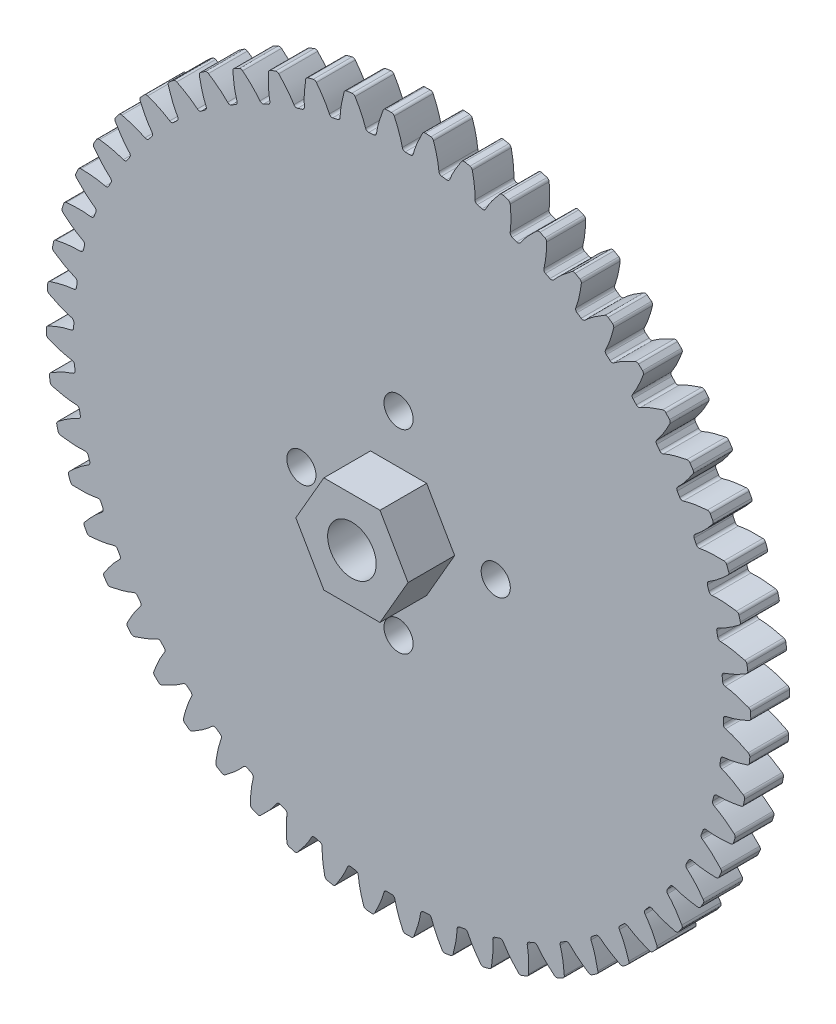
SolidWorks part; units mm, degrees
ref_plane "前视基准面" through (0, 0, 0) normal (0, 0, 1) x (1, 0, 0)
ref_plane "上视基准面" through (0, 0, 0) normal (0, 1, 0) x (1, 0, 0)
ref_plane "右视基准面" through (0, 0, 0) normal (1, 0, 0) x (0, 0, -1)
sketch "草图1" plane through (0, 0, 0) normal (0, 0, 1) x (1, 0, 0)
  circle B0 centre (0, 0) radius 6.5
  circle B1 centre (-10, 0) radius 0.925
  circle B2 centre (0, 10) radius 0.925
  circle B3 centre (0, -10) radius 0.925
  circle B4 centre (10, 0) radius 0.925
  arc B5 (3.3275, 36.097) -> (2.766, 36.1443) centre (0, 0) ccw
  arc B6 (1.1925, 33.4162) -> (0.9378, 33.4243) centre (0, 0) ccw
  arc B7 (4.152, 33.4242) -> (4.4218, 33.1438) centre (4.4631, 33.4536) ccw
  arc B8 (1.1925, 33.4162) -> (1.5054, 33.6474) centre (1.2036, 33.7285) ccw
  arc B9 (2.766, 36.1443) -> (2.4649, 35.9769) centre (2.7421, 35.8327) ccw
  arc B10 (3.5963, 35.8815) -> (3.3275, 36.097) centre (3.2988, 35.7858) ccw
  arc B11 (4.6742, 33.1092) -> (4.4218, 33.1438) centre (0, 0) ccw
  arc B12 (7.3482, 35.4974) -> (6.7954, 35.6074) centre (0, 0) ccw
  arc B13 (4.9264, 33.0726) -> (4.6742, 33.1092) centre (0, 0) ccw
  arc B14 (7.8682, 32.7491) -> (8.1049, 32.4404) centre (8.1807, 32.7435) ccw
  arc B15 (4.9264, 33.0726) -> (5.2633, 33.2673) centre (4.9725, 33.3817) ccw
  arc B16 (6.7954, 35.6074) -> (6.4775, 35.4747) centre (6.7369, 35.3004) ccw
  arc B17 (7.5912, 35.2532) -> (7.3482, 35.4974) centre (7.2848, 35.1914) ccw
  arc B18 (8.3519, 32.3776) -> (8.1049, 32.4404) centre (0, 0) ccw
  arc B19 (11.2764, 34.4515) -> (10.7395, 34.6226) centre (0, 0) ccw
  arc B20 (8.5984, 32.3131) -> (8.3519, 32.3776) centre (0, 0) ccw
  arc B21 (11.4855, 31.6623) -> (11.6861, 31.3289) centre (11.7953, 31.6217) ccw
  arc B22 (8.5984, 32.3131) -> (8.9549, 32.4688) centre (8.6787, 32.6151) ccw
  arc B23 (10.7395, 34.6226) -> (10.4087, 34.5264) centre (10.6469, 34.3242) ccw
  arc B24 (11.4905, 34.1816) -> (11.2764, 34.4515) centre (11.1792, 34.1545) ccw
  arc B25 (11.9245, 31.2389) -> (11.6861, 31.3289) centre (0, 0) ccw
  arc B26 (15.0629, 32.9723) -> (14.5485, 33.2025) centre (0, 0) ccw
  arc B27 (12.1622, 31.1472) -> (11.9245, 31.2389) centre (0, 0) ccw
  arc B28 (14.9583, 30.1772) -> (15.1204, 29.8235) centre (15.2617, 30.1022) ccw
  arc B29 (12.1622, 31.1472) -> (12.534, 31.262) centre (12.2759, 31.4383) ccw
  arc B30 (14.5485, 33.2025) -> (14.2089, 33.1439) centre (14.423, 32.9163) ccw
  arc B31 (15.2454, 32.6801) -> (15.0629, 32.9723) centre (14.933, 32.6881) ccw
  arc B32 (15.3472, 29.7074) -> (15.1204, 29.8235) centre (0, 0) ccw
  arc B33 (18.6599, 31.0785) -> (18.1745, 31.3648) centre (0, 0) ccw
  arc B34 (15.5731, 29.5896) -> (15.3472, 29.7074) centre (0, 0) ccw
  arc B35 (18.243, 28.3127) -> (18.3645, 27.943) centre (18.5361, 28.2042) ccw
  arc B36 (15.5731, 29.5896) -> (15.9554, 29.6621) centre (15.7187, 29.8661) ccw
  arc B37 (18.1745, 31.3648) -> (17.8305, 31.3446) centre (18.0178, 31.0944) ccw
  arc B38 (18.8086, 30.7677) -> (18.6599, 31.0785) centre (18.499, 30.8106) ccw
  arc B39 (18.5769, 27.8023) -> (18.3645, 27.943) centre (0, 0) ccw
  arc B40 (22.0222, 28.7938) -> (21.5719, 29.1327) centre (0, 0) ccw
  arc B41 (18.7882, 27.6599) -> (18.5769, 27.8023) centre (0, 0) ccw
  arc B42 (21.2983, 26.0921) -> (21.3776, 25.7112) centre (21.5774, 25.9514) ccw
  arc B43 (18.7882, 27.6599) -> (19.1762, 27.6892) centre (18.9638, 27.9184) ccw
  arc B44 (21.5719, 29.1327) -> (21.2279, 29.1511) centre (21.386, 28.8815) ccw
  arc B45 (22.1352, 28.4683) -> (22.0222, 28.7938) centre (21.8324, 28.5456) ccw
  arc B46 (21.5729, 25.5475) -> (21.3776, 25.7112) centre (0, 0) ccw
  arc B47 (25.1076, 26.1471) -> (24.6981, 26.5342) centre (0, 0) ccw
  arc B48 (21.767, 25.3824) -> (21.5729, 25.5475) centre (0, 0) ccw
  arc B49 (24.0858, 23.5433) -> (24.1219, 23.156) centre (24.3474, 23.3724) ccw
  arc B50 (21.767, 25.3824) -> (22.1558, 25.368) centre (21.9704, 25.6196) ccw
  arc B51 (24.6981, 26.5342) -> (24.3583, 26.5911) centre (24.4852, 26.3055) ccw
  arc B52 (25.1834, 25.811) -> (25.1076, 26.1471) centre (24.8912, 25.9217) ccw
  arc B53 (24.2977, 22.9715) -> (24.1219, 23.156) centre (0, 0) ccw
  arc B54 (27.8773, 23.1715) -> (27.5137, 23.6021) centre (0, 0) ccw
  arc B55 (24.4721, 22.7856) -> (24.2977, 22.9715) centre (0, 0) ccw
  arc B56 (26.5704, 20.6986) -> (26.5629, 20.3096) centre (26.8112, 20.4994) ccw
  arc B57 (24.4721, 22.7856) -> (24.8568, 22.7278) centre (24.7008, 22.9986) ccw
  arc B58 (27.5137, 23.6021) -> (27.1824, 23.6966) centre (27.2765, 23.3986) ccw
  arc B59 (27.915, 22.829) -> (27.8773, 23.1715) centre (27.637, 22.9717) ccw
  arc B60 (26.7169, 20.1065) -> (26.5629, 20.3096) centre (0, 0) ccw
  arc B61 (30.2964, 19.9045) -> (29.9833, 20.3731) centre (0, 0) ccw
  arc B62 (26.8694, 19.9024) -> (26.7169, 20.1065) centre (0, 0) ccw
  arc B63 (28.7208, 17.5935) -> (28.6698, 17.2077) centre (28.9378, 17.3686) ccw
  arc B64 (26.8694, 19.9024) -> (27.2452, 19.8018) centre (27.1205, 20.0884) ccw
  arc B65 (29.9833, 20.3731) -> (29.6647, 20.5041) centre (29.7248, 20.1975) ccw
  arc B66 (30.2955, 19.56) -> (30.2964, 19.9045) centre (30.0352, 19.7329) ccw
  arc B67 (28.8001, 16.9888) -> (28.6698, 17.2077) centre (0, 0) ccw
  arc B68 (32.3345, 16.3872) -> (32.0759, 16.8879) centre (0, 0) ccw
  arc B69 (28.9288, 16.7688) -> (28.8001, 16.9888) centre (0, 0) ccw
  arc B70 (30.5101, 14.2671) -> (30.4162, 13.8895) centre (30.7005, 14.0194) ccw
  arc B71 (28.9288, 16.7688) -> (29.291, 16.6268) centre (29.1991, 16.9255) ccw
  arc B72 (32.0759, 16.8879) -> (31.7739, 17.0538) centre (31.7993, 16.7423) ccw
  arc B73 (32.2951, 16.045) -> (32.3345, 16.3872) centre (32.0558, 16.246) ccw
  arc B74 (30.5212, 13.6574) -> (30.4162, 13.8895) centre (0, 0) ccw
  arc B75 (33.966, 12.6639) -> (33.765, 13.1904) centre (0, 0) ccw
  arc B76 (30.6244, 13.4244) -> (30.5212, 13.6574) centre (0, 0) ccw
  arc B77 (31.9156, 10.7614) -> (31.7801, 10.3967) centre (32.0771, 10.4938) ccw
  arc B78 (30.6244, 13.4244) -> (30.9685, 13.2427) centre (30.9106, 13.5498) ccw
  arc B79 (33.765, 13.1904) -> (33.4835, 13.389) centre (33.4739, 13.0767) ccw
  arc B80 (33.8885, 12.3282) -> (33.966, 12.6639) centre (33.6732, 12.5547) ccw
  arc B81 (31.8584, 10.1542) -> (31.7801, 10.3967) centre (0, 0) ccw
  arc B82 (35.1703, 8.7813) -> (35.0296, 9.327) centre (0, 0) ccw
  arc B83 (31.9349, 9.9111) -> (31.8584, 10.1542) centre (0, 0) ccw
  arc B84 (32.9199, 7.1203) -> (32.7443, 6.7731) centre (33.0504, 6.8364) ccw
  arc B85 (31.9349, 9.9111) -> (32.2564, 9.6921) centre (32.2333, 10.0037) ccw
  arc B86 (35.0296, 9.327) -> (34.7721, 9.5559) centre (34.7276, 9.2466) ccw
  arc B87 (35.0557, 8.4564) -> (35.1703, 8.7813) centre (34.8671, 8.7056) ccw
  arc B88 (32.795, 6.5233) -> (32.7443, 6.7731) centre (0, 0) ccw
  arc B89 (35.9324, 4.7882) -> (35.8536, 5.3463) centre (0, 0) ccw
  arc B90 (32.8438, 6.2732) -> (32.795, 6.5233) centre (0, 0) ccw
  arc B91 (33.5101, 3.3897) -> (33.2968, 3.0643) centre (33.608, 3.0929) ccw
  arc B92 (32.8438, 6.2732) -> (33.1388, 6.0196) centre (33.1507, 6.3319) ccw
  arc B93 (35.8536, 5.3463) -> (35.6234, 5.6026) centre (35.5445, 5.3002) ccw
  arc B94 (35.7821, 4.4782) -> (35.9324, 4.7882) centre (35.6226, 4.747) ccw
  arc B95 (33.3192, 2.8104) -> (33.2968, 3.0643) centre (0, 0) ccw
  arc B96 (36.2425, 0.735) -> (36.2267, 1.2983) centre (0, 0) ccw
  arc B97 (33.3396, 2.5565) -> (33.3192, 2.8104) centre (0, 0) ccw
  arc B98 (33.6789, -0.3836) -> (33.4305, -0.6831) centre (33.743, -0.6894) ccw
  arc B99 (33.3396, 2.5565) -> (33.6044, 2.2714) centre (33.6512, 2.5803) ccw
  arc B100 (36.2267, 1.2983) -> (36.0266, 1.5788) centre (35.9144, 1.2871) ccw
  arc B101 (36.0585, 0.4437) -> (36.2425, 0.735) centre (35.9301, 0.7286) ccw
  arc B102 (33.4243, -0.9378) -> (33.4305, -0.6831) centre (0, 0) ccw
  arc B103 (36.097, -3.3275) -> (36.1443, -2.766) centre (0, 0) ccw
  arc B104 (33.4162, -1.1925) -> (33.4243, -0.9378) centre (0, 0) ccw
  arc B105 (33.4242, -4.152) -> (33.1438, -4.4218) centre (33.4536, -4.4631) ccw
  arc B106 (33.4162, -1.1925) -> (33.6474, -1.5054) centre (33.7285, -1.2036) ccw
  arc B107 (36.1443, -2.766) -> (35.9769, -2.4649) centre (35.8327, -2.7421) ccw
  arc B108 (35.8815, -3.5963) -> (36.097, -3.3275) centre (35.7858, -3.2988) ccw
  arc B109 (33.1092, -4.6742) -> (33.1438, -4.4218) centre (0, 0) ccw
  arc B110 (35.4974, -7.3482) -> (35.6074, -6.7954) centre (0, 0) ccw
  arc B111 (33.0726, -4.9264) -> (33.1092, -4.6742) centre (0, 0) ccw
  arc B112 (32.7491, -7.8682) -> (32.4404, -8.1049) centre (32.7435, -8.1807) ccw
  arc B113 (33.0726, -4.9264) -> (33.2673, -5.2633) centre (33.3817, -4.9725) ccw
  arc B114 (35.6074, -6.7954) -> (35.4747, -6.4775) centre (35.3004, -6.7369) ccw
  arc B115 (35.2532, -7.5912) -> (35.4974, -7.3482) centre (35.1914, -7.2848) ccw
  arc B116 (32.3776, -8.3519) -> (32.4404, -8.1049) centre (0, 0) ccw
  arc B117 (34.4515, -11.2764) -> (34.6226, -10.7395) centre (0, 0) ccw
  arc B118 (32.3131, -8.5984) -> (32.3776, -8.3519) centre (0, 0) ccw
  arc B119 (31.6623, -11.4855) -> (31.3289, -11.6861) centre (31.6217, -11.7953) ccw
  arc B120 (32.3131, -8.5984) -> (32.4688, -8.9549) centre (32.6151, -8.6787) ccw
  arc B121 (34.6226, -10.7395) -> (34.5264, -10.4087) centre (34.3242, -10.6469) ccw
  arc B122 (34.1816, -11.4905) -> (34.4515, -11.2764) centre (34.1545, -11.1792) ccw
  arc B123 (31.2389, -11.9245) -> (31.3289, -11.6861) centre (0, 0) ccw
  arc B124 (32.9723, -15.0629) -> (33.2025, -14.5485) centre (0, 0) ccw
  arc B125 (31.1472, -12.1622) -> (31.2389, -11.9245) centre (0, 0) ccw
  arc B126 (30.1772, -14.9583) -> (29.8235, -15.1204) centre (30.1022, -15.2617) ccw
  arc B127 (31.1472, -12.1622) -> (31.262, -12.534) centre (31.4383, -12.2759) ccw
  arc B128 (33.2025, -14.5485) -> (33.1439, -14.2089) centre (32.9163, -14.423) ccw
  arc B129 (32.6801, -15.2454) -> (32.9723, -15.0629) centre (32.6881, -14.933) ccw
  arc B130 (29.7074, -15.3472) -> (29.8235, -15.1204) centre (0, 0) ccw
  arc B131 (31.0785, -18.6599) -> (31.3648, -18.1745) centre (0, 0) ccw
  arc B132 (29.5896, -15.5731) -> (29.7074, -15.3472) centre (0, 0) ccw
  arc B133 (28.3127, -18.243) -> (27.943, -18.3645) centre (28.2042, -18.5361) ccw
  arc B134 (29.5896, -15.5731) -> (29.6621, -15.9554) centre (29.8661, -15.7187) ccw
  arc B135 (31.3648, -18.1745) -> (31.3446, -17.8305) centre (31.0944, -18.0178) ccw
  arc B136 (30.7677, -18.8086) -> (31.0785, -18.6599) centre (30.8106, -18.499) ccw
  arc B137 (27.8023, -18.5769) -> (27.943, -18.3645) centre (0, 0) ccw
  arc B138 (28.7938, -22.0222) -> (29.1327, -21.5719) centre (0, 0) ccw
  arc B139 (27.6599, -18.7882) -> (27.8023, -18.5769) centre (0, 0) ccw
  arc B140 (26.0921, -21.2983) -> (25.7112, -21.3776) centre (25.9514, -21.5774) ccw
  arc B141 (27.6599, -18.7882) -> (27.6892, -19.1762) centre (27.9184, -18.9638) ccw
  arc B142 (29.1327, -21.5719) -> (29.1511, -21.2279) centre (28.8815, -21.386) ccw
  arc B143 (28.4683, -22.1352) -> (28.7938, -22.0222) centre (28.5456, -21.8324) ccw
  arc B144 (25.5475, -21.5729) -> (25.7112, -21.3776) centre (0, 0) ccw
  arc B145 (26.1471, -25.1076) -> (26.5342, -24.6981) centre (0, 0) ccw
  arc B146 (25.3824, -21.767) -> (25.5475, -21.5729) centre (0, 0) ccw
  arc B147 (23.5433, -24.0858) -> (23.156, -24.1219) centre (23.3724, -24.3474) ccw
  arc B148 (25.3824, -21.767) -> (25.368, -22.1558) centre (25.6196, -21.9704) ccw
  arc B149 (26.5342, -24.6981) -> (26.5911, -24.3583) centre (26.3055, -24.4852) ccw
  arc B150 (25.811, -25.1834) -> (26.1471, -25.1076) centre (25.9217, -24.8912) ccw
  arc B151 (22.9715, -24.2977) -> (23.156, -24.1219) centre (0, 0) ccw
  arc B152 (23.1715, -27.8773) -> (23.6021, -27.5137) centre (0, 0) ccw
  arc B153 (22.7856, -24.4721) -> (22.9715, -24.2977) centre (0, 0) ccw
  arc B154 (20.6986, -26.5704) -> (20.3096, -26.5629) centre (20.4994, -26.8112) ccw
  arc B155 (22.7856, -24.4721) -> (22.7278, -24.8568) centre (22.9986, -24.7008) ccw
  arc B156 (23.6021, -27.5137) -> (23.6966, -27.1824) centre (23.3986, -27.2765) ccw
  arc B157 (22.829, -27.915) -> (23.1715, -27.8773) centre (22.9717, -27.637) ccw
  arc B158 (20.1065, -26.7169) -> (20.3096, -26.5629) centre (0, 0) ccw
  arc B159 (19.9045, -30.2964) -> (20.3731, -29.9833) centre (0, 0) ccw
  arc B160 (19.9024, -26.8694) -> (20.1065, -26.7169) centre (0, 0) ccw
  arc B161 (17.5935, -28.7208) -> (17.2077, -28.6698) centre (17.3686, -28.9378) ccw
  arc B162 (19.9024, -26.8694) -> (19.8018, -27.2452) centre (20.0884, -27.1205) ccw
  arc B163 (20.3731, -29.9833) -> (20.5041, -29.6647) centre (20.1975, -29.7248) ccw
  arc B164 (19.56, -30.2955) -> (19.9045, -30.2964) centre (19.7329, -30.0352) ccw
  arc B165 (16.9888, -28.8001) -> (17.2077, -28.6698) centre (0, 0) ccw
  arc B166 (16.3872, -32.3345) -> (16.8879, -32.0759) centre (0, 0) ccw
  arc B167 (16.7688, -28.9288) -> (16.9888, -28.8001) centre (0, 0) ccw
  arc B168 (14.2671, -30.5101) -> (13.8895, -30.4162) centre (14.0194, -30.7005) ccw
  arc B169 (16.7688, -28.9288) -> (16.6268, -29.291) centre (16.9255, -29.1991) ccw
  arc B170 (16.8879, -32.0759) -> (17.0538, -31.7739) centre (16.7423, -31.7993) ccw
  arc B171 (16.045, -32.2951) -> (16.3872, -32.3345) centre (16.246, -32.0558) ccw
  arc B172 (13.6574, -30.5212) -> (13.8895, -30.4162) centre (0, 0) ccw
  arc B173 (12.6639, -33.966) -> (13.1904, -33.765) centre (0, 0) ccw
  arc B174 (13.4244, -30.6244) -> (13.6574, -30.5212) centre (0, 0) ccw
  arc B175 (10.7614, -31.9156) -> (10.3967, -31.7801) centre (10.4938, -32.0771) ccw
  arc B176 (13.4244, -30.6244) -> (13.2427, -30.9685) centre (13.5498, -30.9106) ccw
  arc B177 (13.1904, -33.765) -> (13.389, -33.4835) centre (13.0767, -33.4739) ccw
  arc B178 (12.3282, -33.8885) -> (12.6639, -33.966) centre (12.5547, -33.6732) ccw
  arc B179 (10.1542, -31.8584) -> (10.3967, -31.7801) centre (0, 0) ccw
  arc B180 (8.7813, -35.1703) -> (9.327, -35.0296) centre (0, 0) ccw
  arc B181 (9.9111, -31.9349) -> (10.1542, -31.8584) centre (0, 0) ccw
  arc B182 (7.1203, -32.9199) -> (6.7731, -32.7443) centre (6.8364, -33.0504) ccw
  arc B183 (9.9111, -31.9349) -> (9.6921, -32.2564) centre (10.0037, -32.2333) ccw
  arc B184 (9.327, -35.0296) -> (9.5559, -34.7721) centre (9.2466, -34.7276) ccw
  arc B185 (8.4564, -35.0557) -> (8.7813, -35.1703) centre (8.7056, -34.8671) ccw
  arc B186 (6.5233, -32.795) -> (6.7731, -32.7443) centre (0, 0) ccw
  arc B187 (4.7882, -35.9324) -> (5.3463, -35.8536) centre (0, 0) ccw
  arc B188 (6.2732, -32.8438) -> (6.5233, -32.795) centre (0, 0) ccw
  arc B189 (3.3897, -33.5101) -> (3.0643, -33.2968) centre (3.0929, -33.608) ccw
  arc B190 (6.2732, -32.8438) -> (6.0196, -33.1388) centre (6.3319, -33.1507) ccw
  arc B191 (5.3463, -35.8536) -> (5.6026, -35.6234) centre (5.3002, -35.5445) ccw
  arc B192 (4.4782, -35.7821) -> (4.7882, -35.9324) centre (4.747, -35.6226) ccw
  arc B193 (2.8104, -33.3192) -> (3.0643, -33.2968) centre (0, 0) ccw
  arc B194 (0.735, -36.2425) -> (1.2983, -36.2267) centre (0, 0) ccw
  arc B195 (2.5565, -33.3396) -> (2.8104, -33.3192) centre (0, 0) ccw
  arc B196 (-0.3836, -33.6789) -> (-0.6831, -33.4305) centre (-0.6894, -33.743) ccw
  arc B197 (2.5565, -33.3396) -> (2.2714, -33.6044) centre (2.5803, -33.6512) ccw
  arc B198 (1.2983, -36.2267) -> (1.5788, -36.0266) centre (1.2871, -35.9144) ccw
  arc B199 (0.4437, -36.0585) -> (0.735, -36.2425) centre (0.7286, -35.9301) ccw
  arc B200 (-0.9378, -33.4243) -> (-0.6831, -33.4305) centre (0, 0) ccw
  arc B201 (-3.3275, -36.097) -> (-2.766, -36.1443) centre (0, 0) ccw
  arc B202 (-1.1925, -33.4162) -> (-0.9378, -33.4243) centre (0, 0) ccw
  arc B203 (-4.152, -33.4242) -> (-4.4218, -33.1438) centre (-4.4631, -33.4536) ccw
  arc B204 (-1.1925, -33.4162) -> (-1.5054, -33.6474) centre (-1.2036, -33.7285) ccw
  arc B205 (-2.766, -36.1443) -> (-2.4649, -35.9769) centre (-2.7421, -35.8327) ccw
  arc B206 (-3.5963, -35.8815) -> (-3.3275, -36.097) centre (-3.2988, -35.7858) ccw
  arc B207 (-4.6742, -33.1092) -> (-4.4218, -33.1438) centre (0, 0) ccw
  arc B208 (-7.3482, -35.4974) -> (-6.7954, -35.6074) centre (0, 0) ccw
  arc B209 (-4.9264, -33.0726) -> (-4.6742, -33.1092) centre (0, 0) ccw
  arc B210 (-7.8682, -32.7491) -> (-8.1049, -32.4404) centre (-8.1807, -32.7435) ccw
  arc B211 (-4.9264, -33.0726) -> (-5.2633, -33.2673) centre (-4.9725, -33.3817) ccw
  arc B212 (-6.7954, -35.6074) -> (-6.4775, -35.4747) centre (-6.7369, -35.3004) ccw
  arc B213 (-7.5912, -35.2532) -> (-7.3482, -35.4974) centre (-7.2848, -35.1914) ccw
  arc B214 (-8.3519, -32.3776) -> (-8.1049, -32.4404) centre (0, 0) ccw
  arc B215 (-11.2764, -34.4515) -> (-10.7395, -34.6226) centre (0, 0) ccw
  arc B216 (-8.5984, -32.3131) -> (-8.3519, -32.3776) centre (0, 0) ccw
  arc B217 (-11.4855, -31.6623) -> (-11.6861, -31.3289) centre (-11.7953, -31.6217) ccw
  arc B218 (-8.5984, -32.3131) -> (-8.9549, -32.4688) centre (-8.6787, -32.6151) ccw
  arc B219 (-10.7395, -34.6226) -> (-10.4087, -34.5264) centre (-10.6469, -34.3242) ccw
  arc B220 (-11.4905, -34.1816) -> (-11.2764, -34.4515) centre (-11.1792, -34.1545) ccw
  arc B221 (-11.9245, -31.2389) -> (-11.6861, -31.3289) centre (0, 0) ccw
  arc B222 (-15.0629, -32.9723) -> (-14.5485, -33.2025) centre (0, 0) ccw
  arc B223 (-12.1622, -31.1472) -> (-11.9245, -31.2389) centre (0, 0) ccw
  arc B224 (-14.9583, -30.1772) -> (-15.1204, -29.8235) centre (-15.2617, -30.1022) ccw
  arc B225 (-12.1622, -31.1472) -> (-12.534, -31.262) centre (-12.2759, -31.4383) ccw
  arc B226 (-14.5485, -33.2025) -> (-14.2089, -33.1439) centre (-14.423, -32.9163) ccw
  arc B227 (-15.2454, -32.6801) -> (-15.0629, -32.9723) centre (-14.933, -32.6881) ccw
  arc B228 (-15.3472, -29.7074) -> (-15.1204, -29.8235) centre (0, 0) ccw
  arc B229 (-18.6599, -31.0785) -> (-18.1745, -31.3648) centre (0, 0) ccw
  arc B230 (-15.5731, -29.5896) -> (-15.3472, -29.7074) centre (0, 0) ccw
  arc B231 (-18.243, -28.3127) -> (-18.3645, -27.943) centre (-18.5361, -28.2042) ccw
  arc B232 (-15.5731, -29.5896) -> (-15.9554, -29.6621) centre (-15.7187, -29.8661) ccw
  arc B233 (-18.1745, -31.3648) -> (-17.8305, -31.3446) centre (-18.0178, -31.0944) ccw
  arc B234 (-18.8086, -30.7677) -> (-18.6599, -31.0785) centre (-18.499, -30.8106) ccw
  arc B235 (-18.5769, -27.8023) -> (-18.3645, -27.943) centre (0, 0) ccw
  arc B236 (-22.0222, -28.7938) -> (-21.5719, -29.1327) centre (0, 0) ccw
  arc B237 (-18.7882, -27.6599) -> (-18.5769, -27.8023) centre (0, 0) ccw
  arc B238 (-21.2983, -26.0921) -> (-21.3776, -25.7112) centre (-21.5774, -25.9514) ccw
  arc B239 (-18.7882, -27.6599) -> (-19.1762, -27.6892) centre (-18.9638, -27.9184) ccw
  arc B240 (-21.5719, -29.1327) -> (-21.2279, -29.1511) centre (-21.386, -28.8815) ccw
  arc B241 (-22.1352, -28.4683) -> (-22.0222, -28.7938) centre (-21.8324, -28.5456) ccw
  arc B242 (-21.5729, -25.5475) -> (-21.3776, -25.7112) centre (0, 0) ccw
  arc B243 (-25.1076, -26.1471) -> (-24.6981, -26.5342) centre (0, 0) ccw
  arc B244 (-21.767, -25.3824) -> (-21.5729, -25.5475) centre (0, 0) ccw
  arc B245 (-24.0858, -23.5433) -> (-24.1219, -23.156) centre (-24.3474, -23.3724) ccw
  arc B246 (-21.767, -25.3824) -> (-22.1558, -25.368) centre (-21.9704, -25.6196) ccw
  arc B247 (-24.6981, -26.5342) -> (-24.3583, -26.5911) centre (-24.4852, -26.3055) ccw
  arc B248 (-25.1834, -25.811) -> (-25.1076, -26.1471) centre (-24.8912, -25.9217) ccw
  arc B249 (-24.2977, -22.9715) -> (-24.1219, -23.156) centre (0, 0) ccw
  arc B250 (-27.8773, -23.1715) -> (-27.5137, -23.6021) centre (0, 0) ccw
  arc B251 (-24.4721, -22.7856) -> (-24.2977, -22.9715) centre (0, 0) ccw
  arc B252 (-26.5704, -20.6986) -> (-26.5629, -20.3096) centre (-26.8112, -20.4994) ccw
  arc B253 (-24.4721, -22.7856) -> (-24.8568, -22.7278) centre (-24.7008, -22.9986) ccw
  arc B254 (-27.5137, -23.6021) -> (-27.1824, -23.6966) centre (-27.2765, -23.3986) ccw
  arc B255 (-27.915, -22.829) -> (-27.8773, -23.1715) centre (-27.637, -22.9717) ccw
  arc B256 (-26.7169, -20.1065) -> (-26.5629, -20.3096) centre (0, 0) ccw
  arc B257 (-30.2964, -19.9045) -> (-29.9833, -20.3731) centre (0, 0) ccw
  arc B258 (-26.8694, -19.9024) -> (-26.7169, -20.1065) centre (0, 0) ccw
  arc B259 (-28.7208, -17.5935) -> (-28.6698, -17.2077) centre (-28.9378, -17.3686) ccw
  arc B260 (-26.8694, -19.9024) -> (-27.2452, -19.8018) centre (-27.1205, -20.0884) ccw
  arc B261 (-29.9833, -20.3731) -> (-29.6647, -20.5041) centre (-29.7248, -20.1975) ccw
  arc B262 (-30.2955, -19.56) -> (-30.2964, -19.9045) centre (-30.0352, -19.7329) ccw
  arc B263 (-28.8001, -16.9888) -> (-28.6698, -17.2077) centre (0, 0) ccw
  arc B264 (-32.3345, -16.3872) -> (-32.0759, -16.8879) centre (0, 0) ccw
  arc B265 (-28.9288, -16.7688) -> (-28.8001, -16.9888) centre (0, 0) ccw
  arc B266 (-30.5101, -14.2671) -> (-30.4162, -13.8895) centre (-30.7005, -14.0194) ccw
  arc B267 (-28.9288, -16.7688) -> (-29.291, -16.6268) centre (-29.1991, -16.9255) ccw
  arc B268 (-32.0759, -16.8879) -> (-31.7739, -17.0538) centre (-31.7993, -16.7423) ccw
  arc B269 (-32.2951, -16.045) -> (-32.3345, -16.3872) centre (-32.0558, -16.246) ccw
  arc B270 (-30.5212, -13.6574) -> (-30.4162, -13.8895) centre (0, 0) ccw
  arc B271 (-33.966, -12.6639) -> (-33.765, -13.1904) centre (0, 0) ccw
  arc B272 (-30.6244, -13.4244) -> (-30.5212, -13.6574) centre (0, 0) ccw
  arc B273 (-31.9156, -10.7614) -> (-31.7801, -10.3967) centre (-32.0771, -10.4938) ccw
  arc B274 (-30.6244, -13.4244) -> (-30.9685, -13.2427) centre (-30.9106, -13.5498) ccw
  arc B275 (-33.765, -13.1904) -> (-33.4835, -13.389) centre (-33.4739, -13.0767) ccw
  arc B276 (-33.8885, -12.3282) -> (-33.966, -12.6639) centre (-33.6732, -12.5547) ccw
  arc B277 (-31.8584, -10.1542) -> (-31.7801, -10.3967) centre (0, 0) ccw
  arc B278 (-35.1703, -8.7813) -> (-35.0296, -9.327) centre (0, 0) ccw
  arc B279 (-31.9349, -9.9111) -> (-31.8584, -10.1542) centre (0, 0) ccw
  arc B280 (-32.9199, -7.1203) -> (-32.7443, -6.7731) centre (-33.0504, -6.8364) ccw
  arc B281 (-31.9349, -9.9111) -> (-32.2564, -9.6921) centre (-32.2333, -10.0037) ccw
  arc B282 (-35.0296, -9.327) -> (-34.7721, -9.5559) centre (-34.7276, -9.2466) ccw
  arc B283 (-35.0557, -8.4564) -> (-35.1703, -8.7813) centre (-34.8671, -8.7056) ccw
  arc B284 (-32.795, -6.5233) -> (-32.7443, -6.7731) centre (0, 0) ccw
  arc B285 (-35.9324, -4.7882) -> (-35.8536, -5.3463) centre (0, 0) ccw
  arc B286 (-32.8438, -6.2732) -> (-32.795, -6.5233) centre (0, 0) ccw
  arc B287 (-33.5101, -3.3897) -> (-33.2968, -3.0643) centre (-33.608, -3.0929) ccw
  arc B288 (-32.8438, -6.2732) -> (-33.1388, -6.0196) centre (-33.1507, -6.3319) ccw
  arc B289 (-35.8536, -5.3463) -> (-35.6234, -5.6026) centre (-35.5445, -5.3002) ccw
  arc B290 (-35.7821, -4.4782) -> (-35.9324, -4.7882) centre (-35.6226, -4.747) ccw
  arc B291 (-33.3192, -2.8104) -> (-33.2968, -3.0643) centre (0, 0) ccw
  arc B292 (-36.2425, -0.735) -> (-36.2267, -1.2983) centre (0, 0) ccw
  arc B293 (-33.3396, -2.5565) -> (-33.3192, -2.8104) centre (0, 0) ccw
  arc B294 (-33.6789, 0.3836) -> (-33.4305, 0.6831) centre (-33.743, 0.6894) ccw
  arc B295 (-33.3396, -2.5565) -> (-33.6044, -2.2714) centre (-33.6512, -2.5803) ccw
  arc B296 (-36.2267, -1.2983) -> (-36.0266, -1.5788) centre (-35.9144, -1.2871) ccw
  arc B297 (-36.0585, -0.4437) -> (-36.2425, -0.735) centre (-35.9301, -0.7286) ccw
  arc B298 (-33.4243, 0.9378) -> (-33.4305, 0.6831) centre (0, 0) ccw
  arc B299 (-36.097, 3.3275) -> (-36.1443, 2.766) centre (0, 0) ccw
  arc B300 (-33.4162, 1.1925) -> (-33.4243, 0.9378) centre (0, 0) ccw
  arc B301 (-33.4242, 4.152) -> (-33.1438, 4.4218) centre (-33.4536, 4.4631) ccw
  arc B302 (-33.4162, 1.1925) -> (-33.6474, 1.5054) centre (-33.7285, 1.2036) ccw
  arc B303 (-36.1443, 2.766) -> (-35.9769, 2.4649) centre (-35.8327, 2.7421) ccw
  arc B304 (-35.8815, 3.5963) -> (-36.097, 3.3275) centre (-35.7858, 3.2988) ccw
  arc B305 (-33.1092, 4.6742) -> (-33.1438, 4.4218) centre (0, 0) ccw
  arc B306 (-35.4974, 7.3482) -> (-35.6074, 6.7954) centre (0, 0) ccw
  arc B307 (-33.0726, 4.9264) -> (-33.1092, 4.6742) centre (0, 0) ccw
  arc B308 (-32.7491, 7.8682) -> (-32.4404, 8.1049) centre (-32.7435, 8.1807) ccw
  arc B309 (-33.0726, 4.9264) -> (-33.2673, 5.2633) centre (-33.3817, 4.9725) ccw
  arc B310 (-35.6074, 6.7954) -> (-35.4747, 6.4775) centre (-35.3004, 6.7369) ccw
  arc B311 (-35.2532, 7.5912) -> (-35.4974, 7.3482) centre (-35.1914, 7.2848) ccw
  arc B312 (-32.3776, 8.3519) -> (-32.4404, 8.1049) centre (0, 0) ccw
  arc B313 (-34.4515, 11.2764) -> (-34.6226, 10.7395) centre (0, 0) ccw
  arc B314 (-32.3131, 8.5984) -> (-32.3776, 8.3519) centre (0, 0) ccw
  arc B315 (-31.6623, 11.4855) -> (-31.3289, 11.6861) centre (-31.6217, 11.7953) ccw
  arc B316 (-32.3131, 8.5984) -> (-32.4688, 8.9549) centre (-32.6151, 8.6787) ccw
  arc B317 (-34.6226, 10.7395) -> (-34.5264, 10.4087) centre (-34.3242, 10.6469) ccw
  arc B318 (-34.1816, 11.4905) -> (-34.4515, 11.2764) centre (-34.1545, 11.1792) ccw
  arc B319 (-31.2389, 11.9245) -> (-31.3289, 11.6861) centre (0, 0) ccw
  arc B320 (-32.9723, 15.0629) -> (-33.2025, 14.5485) centre (0, 0) ccw
  arc B321 (-31.1472, 12.1622) -> (-31.2389, 11.9245) centre (0, 0) ccw
  arc B322 (-30.1772, 14.9583) -> (-29.8235, 15.1204) centre (-30.1022, 15.2617) ccw
  arc B323 (-31.1472, 12.1622) -> (-31.262, 12.534) centre (-31.4383, 12.2759) ccw
  arc B324 (-33.2025, 14.5485) -> (-33.1439, 14.2089) centre (-32.9163, 14.423) ccw
  arc B325 (-32.6801, 15.2454) -> (-32.9723, 15.0629) centre (-32.6881, 14.933) ccw
  arc B326 (-29.7074, 15.3472) -> (-29.8235, 15.1204) centre (0, 0) ccw
  arc B327 (-31.0785, 18.6599) -> (-31.3648, 18.1745) centre (0, 0) ccw
  arc B328 (-29.5896, 15.5731) -> (-29.7074, 15.3472) centre (0, 0) ccw
  arc B329 (-28.3127, 18.243) -> (-27.943, 18.3645) centre (-28.2042, 18.5361) ccw
  arc B330 (-29.5896, 15.5731) -> (-29.6621, 15.9554) centre (-29.8661, 15.7187) ccw
  arc B331 (-31.3648, 18.1745) -> (-31.3446, 17.8305) centre (-31.0944, 18.0178) ccw
  arc B332 (-30.7677, 18.8086) -> (-31.0785, 18.6599) centre (-30.8106, 18.499) ccw
  arc B333 (-27.8023, 18.5769) -> (-27.943, 18.3645) centre (0, 0) ccw
  arc B334 (-28.7938, 22.0222) -> (-29.1327, 21.5719) centre (0, 0) ccw
  arc B335 (-27.6599, 18.7882) -> (-27.8023, 18.5769) centre (0, 0) ccw
  arc B336 (-26.0921, 21.2983) -> (-25.7112, 21.3776) centre (-25.9514, 21.5774) ccw
  arc B337 (-27.6599, 18.7882) -> (-27.6892, 19.1762) centre (-27.9184, 18.9638) ccw
  arc B338 (-29.1327, 21.5719) -> (-29.1511, 21.2279) centre (-28.8815, 21.386) ccw
  arc B339 (-28.4683, 22.1352) -> (-28.7938, 22.0222) centre (-28.5456, 21.8324) ccw
  arc B340 (-25.5475, 21.5729) -> (-25.7112, 21.3776) centre (0, 0) ccw
  arc B341 (-26.1471, 25.1076) -> (-26.5342, 24.6981) centre (0, 0) ccw
  arc B342 (-25.3824, 21.767) -> (-25.5475, 21.5729) centre (0, 0) ccw
  arc B343 (-23.5433, 24.0858) -> (-23.156, 24.1219) centre (-23.3724, 24.3474) ccw
  arc B344 (-25.3824, 21.767) -> (-25.368, 22.1558) centre (-25.6196, 21.9704) ccw
  arc B345 (-26.5342, 24.6981) -> (-26.5911, 24.3583) centre (-26.3055, 24.4852) ccw
  arc B346 (-25.811, 25.1834) -> (-26.1471, 25.1076) centre (-25.9217, 24.8912) ccw
  arc B347 (-22.9715, 24.2977) -> (-23.156, 24.1219) centre (0, 0) ccw
  arc B348 (-23.1715, 27.8773) -> (-23.6021, 27.5137) centre (0, 0) ccw
  arc B349 (-22.7856, 24.4721) -> (-22.9715, 24.2977) centre (0, 0) ccw
  arc B350 (-20.6986, 26.5704) -> (-20.3096, 26.5629) centre (-20.4994, 26.8112) ccw
  arc B351 (-22.7856, 24.4721) -> (-22.7278, 24.8568) centre (-22.9986, 24.7008) ccw
  arc B352 (-23.6021, 27.5137) -> (-23.6966, 27.1824) centre (-23.3986, 27.2765) ccw
  arc B353 (-22.829, 27.915) -> (-23.1715, 27.8773) centre (-22.9717, 27.637) ccw
  arc B354 (-20.1065, 26.7169) -> (-20.3096, 26.5629) centre (0, 0) ccw
  arc B355 (-19.9045, 30.2964) -> (-20.3731, 29.9833) centre (0, 0) ccw
  arc B356 (-19.9024, 26.8694) -> (-20.1065, 26.7169) centre (0, 0) ccw
  arc B357 (-17.5935, 28.7208) -> (-17.2077, 28.6698) centre (-17.3686, 28.9378) ccw
  arc B358 (-19.9024, 26.8694) -> (-19.8018, 27.2452) centre (-20.0884, 27.1205) ccw
  arc B359 (-20.3731, 29.9833) -> (-20.5041, 29.6647) centre (-20.1975, 29.7248) ccw
  arc B360 (-19.56, 30.2955) -> (-19.9045, 30.2964) centre (-19.7329, 30.0352) ccw
  arc B361 (-16.9888, 28.8001) -> (-17.2077, 28.6698) centre (0, 0) ccw
  arc B362 (-16.3872, 32.3345) -> (-16.8879, 32.0759) centre (0, 0) ccw
  arc B363 (-16.7688, 28.9288) -> (-16.9888, 28.8001) centre (0, 0) ccw
  arc B364 (-14.2671, 30.5101) -> (-13.8895, 30.4162) centre (-14.0194, 30.7005) ccw
  arc B365 (-16.7688, 28.9288) -> (-16.6268, 29.291) centre (-16.9255, 29.1991) ccw
  arc B366 (-16.8879, 32.0759) -> (-17.0538, 31.7739) centre (-16.7423, 31.7993) ccw
  arc B367 (-16.045, 32.2951) -> (-16.3872, 32.3345) centre (-16.246, 32.0558) ccw
  arc B368 (-13.6574, 30.5212) -> (-13.8895, 30.4162) centre (0, 0) ccw
  arc B369 (-12.6639, 33.966) -> (-13.1904, 33.765) centre (0, 0) ccw
  arc B370 (-13.4244, 30.6244) -> (-13.6574, 30.5212) centre (0, 0) ccw
  arc B371 (-10.7614, 31.9156) -> (-10.3967, 31.7801) centre (-10.4938, 32.0771) ccw
  arc B372 (-13.4244, 30.6244) -> (-13.2427, 30.9685) centre (-13.5498, 30.9106) ccw
  arc B373 (-13.1904, 33.765) -> (-13.389, 33.4835) centre (-13.0767, 33.4739) ccw
  arc B374 (-12.3282, 33.8885) -> (-12.6639, 33.966) centre (-12.5547, 33.6732) ccw
  arc B375 (-10.1542, 31.8584) -> (-10.3967, 31.7801) centre (0, 0) ccw
  arc B376 (-8.7813, 35.1703) -> (-9.327, 35.0296) centre (0, 0) ccw
  arc B377 (-9.9111, 31.9349) -> (-10.1542, 31.8584) centre (0, 0) ccw
  arc B378 (-7.1203, 32.9199) -> (-6.7731, 32.7443) centre (-6.8364, 33.0504) ccw
  arc B379 (-9.9111, 31.9349) -> (-9.6921, 32.2564) centre (-10.0037, 32.2333) ccw
  arc B380 (-9.327, 35.0296) -> (-9.5559, 34.7721) centre (-9.2466, 34.7276) ccw
  arc B381 (-8.4564, 35.0557) -> (-8.7813, 35.1703) centre (-8.7056, 34.8671) ccw
  arc B382 (-6.5233, 32.795) -> (-6.7731, 32.7443) centre (0, 0) ccw
  arc B383 (-4.7882, 35.9324) -> (-5.3463, 35.8536) centre (0, 0) ccw
  arc B384 (-6.2732, 32.8438) -> (-6.5233, 32.795) centre (0, 0) ccw
  arc B385 (-3.3897, 33.5101) -> (-3.0643, 33.2968) centre (-3.0929, 33.608) ccw
  arc B386 (-6.2732, 32.8438) -> (-6.0196, 33.1388) centre (-6.3319, 33.1507) ccw
  arc B387 (-5.3463, 35.8536) -> (-5.6026, 35.6234) centre (-5.3002, 35.5445) ccw
  arc B388 (-4.4782, 35.7821) -> (-4.7882, 35.9324) centre (-4.747, 35.6226) ccw
  arc B389 (-2.8104, 33.3192) -> (-3.0643, 33.2968) centre (0, 0) ccw
  arc B390 (0.9378, 33.4243) -> (0.6831, 33.4305) centre (0, 0) ccw
  arc B391 (-0.4437, 36.0585) -> (-0.735, 36.2425) centre (-0.7286, 35.9301) ccw
  arc B392 (-1.2983, 36.2267) -> (-1.5788, 36.0266) centre (-1.2871, 35.9144) ccw
  arc B393 (-2.5565, 33.3396) -> (-2.2714, 33.6044) centre (-2.5803, 33.6512) ccw
  arc B394 (0.3836, 33.6789) -> (0.6831, 33.4305) centre (0.6894, 33.743) ccw
  arc B395 (-2.5565, 33.3396) -> (-2.8104, 33.3192) centre (0, 0) ccw
  arc B396 (-0.735, 36.2425) -> (-1.2983, 36.2267) centre (0, 0) ccw
  spline B397 degree 3 poles (2.4649, 35.9769) (2.3009, 35.6616) (1.9902, 35.0512) (1.6861, 34.2646) (1.5461, 33.7988) (1.5054, 33.6474) knots 0.205794 0.205794 0.205794 0.205794 1.271237 2.259978 2.73007 2.73007 2.73007 2.73007
  spline B398 degree 3 poles (3.5963, 35.8815) (3.7051, 35.5432) (3.9092, 34.8894) (4.0772, 34.0629) (4.1373, 33.5802) (4.152, 33.4242) knots 0.205794 0.205794 0.205794 0.205794 1.271237 2.259978 2.73007 2.73007 2.73007 2.73007
  spline B399 degree 3 poles (6.4775, 35.4747) (6.2793, 35.1797) (5.9022, 34.608) (5.512, 33.8604) (5.3206, 33.4132) (5.2633, 33.2673) knots 0.205794 0.205794 0.205794 0.205794 1.271237 2.259978 2.73007 2.73007 2.73007 2.73007
  spline B400 degree 3 poles (7.5912, 35.2532) (7.6614, 34.9048) (7.791, 34.2323) (7.8654, 33.3922) (7.871, 32.9059) (7.8682, 32.7491) knots 0.205794 0.205794 0.205794 0.205794 1.271237 2.259978 2.73007 2.73007 2.73007 2.73007
  spline B401 degree 3 poles (10.4087, 34.5264) (10.1787, 34.2555) (9.7399, 33.7296) (9.2685, 33.0303) (9.0283, 32.6073) (8.9549, 32.4688) knots 0.205794 0.205794 0.205794 0.205794 1.271237 2.259978 2.73007 2.73007 2.73007 2.73007
  spline B402 degree 3 poles (11.4905, 34.1816) (11.5213, 33.8275) (11.5748, 33.1447) (11.5547, 32.3016) (11.5058, 31.8177) (11.4855, 31.6623) knots 0.205794 0.205794 0.205794 0.205794 1.271237 2.259978 2.73007 2.73007 2.73007 2.73007
  spline B403 degree 3 poles (14.2089, 33.1439) (13.9501, 32.9004) (13.4552, 32.4269) (12.9084, 31.7849) (12.6224, 31.3915) (12.534, 31.262) knots 0.205794 0.205794 0.205794 0.205794 1.271237 2.259978 2.73007 2.73007 2.73007 2.73007
  spline B404 degree 3 poles (15.2454, 32.6801) (15.2364, 32.3249) (15.2131, 31.6403) (15.0987, 30.8048) (14.9959, 30.3294) (14.9583, 30.1772) knots 0.205794 0.205794 0.205794 0.205794 1.271237 2.259978 2.73007 2.73007 2.73007 2.73007
  spline B405 degree 3 poles (17.8305, 31.3446) (17.5461, 31.1317) (17.0013, 30.7165) (16.386, 30.1398) (16.0577, 29.7808) (15.9554, 29.6621) knots 0.205794 0.205794 0.205794 0.205794 1.271237 2.259978 2.73007 2.73007 2.73007 2.73007
  spline B406 degree 3 poles (18.8086, 30.7677) (18.7598, 30.4157) (18.66, 29.7381) (18.4528, 28.9206) (18.2975, 28.4597) (18.243, 28.3127) knots 0.205794 0.205794 0.205794 0.205794 1.271237 2.259978 2.73007 2.73007 2.73007 2.73007
  spline B407 degree 3 poles (21.2279, 29.1511) (20.9214, 28.9714) (20.3335, 28.6199) (19.6576, 28.1156) (19.2912, 27.7957) (19.1762, 27.6892) knots 0.205794 0.205794 0.205794 0.205794 1.271237 2.259978 2.73007 2.73007 2.73007 2.73007
  spline B408 degree 3 poles (22.1352, 28.4683) (22.0473, 28.124) (21.8723, 27.4618) (21.5748, 26.6727) (21.3689, 26.232) (21.2983, 26.0921) knots 0.205794 0.205794 0.205794 0.205794 1.271237 2.259978 2.73007 2.73007 2.73007 2.73007
  spline B409 degree 3 poles (24.3583, 26.5911) (24.0336, 26.4468) (23.4101, 26.1633) (22.6819, 25.7379) (22.282, 25.461) (22.1558, 25.368) knots 0.205794 0.205794 0.205794 0.205794 1.271237 2.259978 2.73007 2.73007 2.73007 2.73007
  spline B410 degree 3 poles (25.1834, 25.811) (25.0576, 25.4787) (24.8095, 24.8402) (24.4256, 24.0894) (24.1716, 23.6745) (24.0858, 23.5433) knots 0.205794 0.205794 0.205794 0.205794 1.271237 2.259978 2.73007 2.73007 2.73007 2.73007
  spline B411 degree 3 poles (27.1824, 23.6966) (26.8436, 23.5896) (26.1922, 23.3777) (25.421, 23.0365) (24.9926, 22.8061) (24.8568, 22.7278) knots 0.205794 0.205794 0.205794 0.205794 1.271237 2.259978 2.73007 2.73007 2.73007 2.73007
  spline B412 degree 3 poles (27.915, 22.829) (27.7527, 22.5129) (27.4347, 21.9063) (26.9692, 21.2031) (26.6703, 20.8193) (26.5704, 20.6986) knots 0.205794 0.205794 0.205794 0.205794 1.271237 2.259978 2.73007 2.73007 2.73007 2.73007
  spline B413 degree 3 poles (29.6647, 20.5041) (29.316, 20.4357) (28.645, 20.2981) (27.8404, 20.0454) (27.3889, 19.8644) (27.2452, 19.8018) knots 0.205794 0.205794 0.205794 0.205794 1.271237 2.259978 2.73007 2.73007 2.73007 2.73007
  spline B414 degree 3 poles (30.2955, 19.56) (30.0989, 19.264) (29.715, 18.6968) (29.1736, 18.0502) (28.8336, 17.7023) (28.7208, 17.5935) knots 0.205794 0.205794 0.205794 0.205794 1.271237 2.259978 2.73007 2.73007 2.73007 2.73007
  spline B415 degree 3 poles (31.7739, 17.0538) (31.4197, 17.0249) (30.7376, 16.9632) (29.9097, 16.8022) (29.4408, 16.6729) (29.291, 16.6268) knots 0.205794 0.205794 0.205794 0.205794 1.271237 2.259978 2.73007 2.73007 2.73007 2.73007
  spline B416 degree 3 poles (32.2951, 16.045) (32.0665, 15.7729) (31.6215, 15.2522) (31.0111, 14.6703) (30.6343, 14.3626) (30.5101, 14.2671) knots 0.205794 0.205794 0.205794 0.205794 1.271237 2.259978 2.73007 2.73007 2.73007 2.73007
  spline B417 degree 3 poles (33.4835, 13.389) (33.1283, 13.3999) (32.4436, 13.4151) (31.6029, 13.3477) (31.1225, 13.2718) (30.9685, 13.2427) knots 0.205794 0.205794 0.205794 0.205794 1.271237 2.259978 2.73007 2.73007 2.73007 2.73007
  spline B418 degree 3 poles (33.8885, 12.3282) (33.6309, 12.0834) (33.1304, 11.6158) (32.4587, 11.1059) (32.0498, 10.8424) (31.9156, 10.7614) knots 0.205794 0.205794 0.205794 0.205794 1.271237 2.259978 2.73007 2.73007 2.73007 2.73007
  spline B419 degree 3 poles (34.7721, 9.5559) (34.4203, 9.6065) (33.7416, 9.6982) (32.8987, 9.7254) (32.4128, 9.7037) (32.2564, 9.6921) knots 0.205794 0.205794 0.205794 0.205794 1.271237 2.259978 2.73007 2.73007 2.73007 2.73007
  spline B420 degree 3 poles (35.0557, 8.4564) (34.7723, 8.242) (34.2226, 7.8334) (33.498, 7.4018) (33.0623, 7.1858) (32.9199, 7.1203) knots 0.205794 0.205794 0.205794 0.205794 1.271237 2.259978 2.73007 2.73007 2.73007 2.73007
  spline B421 degree 3 poles (35.6234, 5.6026) (35.2795, 5.6922) (34.6153, 5.8593) (33.7807, 5.9807) (33.2954, 6.0136) (33.1388, 6.0196) knots 0.205794 0.205794 0.205794 0.205794 1.271237 2.259978 2.73007 2.73007 2.73007 2.73007
  spline B422 degree 3 poles (35.7821, 4.4782) (35.4765, 4.2969) (34.8845, 3.9524) (34.1162, 3.6047) (33.6589, 3.4388) (33.5101, 3.3897) knots 0.205794 0.205794 0.205794 0.205794 1.271237 2.259978 2.73007 2.73007 2.73007 2.73007
  spline B423 degree 3 poles (36.0266, 1.5788) (35.695, 1.7064) (35.0537, 1.9468) (34.2379, 2.1609) (33.7594, 2.2479) (33.6044, 2.2714) knots 0.205794 0.205794 0.205794 0.205794 1.271237 2.259978 2.73007 2.73007 2.73007 2.73007
  spline B424 degree 3 poles (36.0585, 0.4437) (35.7345, 0.2977) (35.1077, 0.0217) (34.3052, -0.2377) (33.8323, -0.3515) (33.6789, -0.3836) knots 0.205794 0.205794 0.205794 0.205794 1.271237 2.259978 2.73007 2.73007 2.73007 2.73007
  spline B425 degree 3 poles (35.9769, -2.4649) (35.6616, -2.3009) (35.0512, -1.9902) (34.2646, -1.6861) (33.7988, -1.5461) (33.6474, -1.5054) knots 0.205794 0.205794 0.205794 0.205794 1.271237 2.259978 2.73007 2.73007 2.73007 2.73007
  spline B426 degree 3 poles (35.8815, -3.5963) (35.5432, -3.7051) (34.8894, -3.9092) (34.0629, -4.0772) (33.5802, -4.1373) (33.4242, -4.152) knots 0.205794 0.205794 0.205794 0.205794 1.271237 2.259978 2.73007 2.73007 2.73007 2.73007
  spline B427 degree 3 poles (35.4747, -6.4775) (35.1797, -6.2793) (34.608, -5.9022) (33.8604, -5.512) (33.4132, -5.3206) (33.2673, -5.2633) knots 0.205794 0.205794 0.205794 0.205794 1.271237 2.259978 2.73007 2.73007 2.73007 2.73007
  spline B428 degree 3 poles (35.2532, -7.5912) (34.9048, -7.6614) (34.2323, -7.791) (33.3922, -7.8654) (32.9059, -7.871) (32.7491, -7.8682) knots 0.205794 0.205794 0.205794 0.205794 1.271237 2.259978 2.73007 2.73007 2.73007 2.73007
  spline B429 degree 3 poles (34.5264, -10.4087) (34.2555, -10.1787) (33.7296, -9.7399) (33.0303, -9.2685) (32.6073, -9.0283) (32.4688, -8.9549) knots 0.205794 0.205794 0.205794 0.205794 1.271237 2.259978 2.73007 2.73007 2.73007 2.73007
  spline B430 degree 3 poles (34.1816, -11.4905) (33.8275, -11.5213) (33.1447, -11.5748) (32.3016, -11.5547) (31.8177, -11.5058) (31.6623, -11.4855) knots 0.205794 0.205794 0.205794 0.205794 1.271237 2.259978 2.73007 2.73007 2.73007 2.73007
  spline B431 degree 3 poles (33.1439, -14.2089) (32.9004, -13.9501) (32.4269, -13.4552) (31.7849, -12.9084) (31.3915, -12.6224) (31.262, -12.534) knots 0.205794 0.205794 0.205794 0.205794 1.271237 2.259978 2.73007 2.73007 2.73007 2.73007
  spline B432 degree 3 poles (32.6801, -15.2454) (32.3249, -15.2364) (31.6403, -15.2131) (30.8048, -15.0987) (30.3294, -14.9959) (30.1772, -14.9583) knots 0.205794 0.205794 0.205794 0.205794 1.271237 2.259978 2.73007 2.73007 2.73007 2.73007
  spline B433 degree 3 poles (31.3446, -17.8305) (31.1317, -17.5461) (30.7165, -17.0013) (30.1398, -16.386) (29.7808, -16.0577) (29.6621, -15.9554) knots 0.205794 0.205794 0.205794 0.205794 1.271237 2.259978 2.73007 2.73007 2.73007 2.73007
  spline B434 degree 3 poles (30.7677, -18.8086) (30.4157, -18.7598) (29.7381, -18.66) (28.9206, -18.4528) (28.4597, -18.2975) (28.3127, -18.243) knots 0.205794 0.205794 0.205794 0.205794 1.271237 2.259978 2.73007 2.73007 2.73007 2.73007
  spline B435 degree 3 poles (29.1511, -21.2279) (28.9714, -20.9214) (28.6199, -20.3335) (28.1156, -19.6576) (27.7957, -19.2912) (27.6892, -19.1762) knots 0.205794 0.205794 0.205794 0.205794 1.271237 2.259978 2.73007 2.73007 2.73007 2.73007
  spline B436 degree 3 poles (28.4683, -22.1352) (28.124, -22.0473) (27.4618, -21.8723) (26.6727, -21.5748) (26.232, -21.3689) (26.0921, -21.2983) knots 0.205794 0.205794 0.205794 0.205794 1.271237 2.259978 2.73007 2.73007 2.73007 2.73007
  spline B437 degree 3 poles (26.5911, -24.3583) (26.4468, -24.0336) (26.1633, -23.4101) (25.7379, -22.6819) (25.461, -22.282) (25.368, -22.1558) knots 0.205794 0.205794 0.205794 0.205794 1.271237 2.259978 2.73007 2.73007 2.73007 2.73007
  spline B438 degree 3 poles (25.811, -25.1834) (25.4787, -25.0576) (24.8402, -24.8095) (24.0894, -24.4256) (23.6745, -24.1716) (23.5433, -24.0858) knots 0.205794 0.205794 0.205794 0.205794 1.271237 2.259978 2.73007 2.73007 2.73007 2.73007
  spline B439 degree 3 poles (23.6966, -27.1824) (23.5896, -26.8436) (23.3777, -26.1922) (23.0365, -25.421) (22.8061, -24.9926) (22.7278, -24.8568) knots 0.205794 0.205794 0.205794 0.205794 1.271237 2.259978 2.73007 2.73007 2.73007 2.73007
  spline B440 degree 3 poles (22.829, -27.915) (22.5129, -27.7527) (21.9063, -27.4347) (21.2031, -26.9692) (20.8193, -26.6703) (20.6986, -26.5704) knots 0.205794 0.205794 0.205794 0.205794 1.271237 2.259978 2.73007 2.73007 2.73007 2.73007
  spline B441 degree 3 poles (20.5041, -29.6647) (20.4357, -29.316) (20.2981, -28.645) (20.0454, -27.8404) (19.8644, -27.3889) (19.8018, -27.2452) knots 0.205794 0.205794 0.205794 0.205794 1.271237 2.259978 2.73007 2.73007 2.73007 2.73007
  spline B442 degree 3 poles (19.56, -30.2955) (19.264, -30.0989) (18.6968, -29.715) (18.0502, -29.1736) (17.7023, -28.8336) (17.5935, -28.7208) knots 0.205794 0.205794 0.205794 0.205794 1.271237 2.259978 2.73007 2.73007 2.73007 2.73007
  spline B443 degree 3 poles (17.0538, -31.7739) (17.0249, -31.4197) (16.9632, -30.7376) (16.8022, -29.9097) (16.6729, -29.4408) (16.6268, -29.291) knots 0.205794 0.205794 0.205794 0.205794 1.271237 2.259978 2.73007 2.73007 2.73007 2.73007
  spline B444 degree 3 poles (16.045, -32.2951) (15.7729, -32.0665) (15.2522, -31.6215) (14.6703, -31.0111) (14.3626, -30.6343) (14.2671, -30.5101) knots 0.205794 0.205794 0.205794 0.205794 1.271237 2.259978 2.73007 2.73007 2.73007 2.73007
  spline B445 degree 3 poles (13.389, -33.4835) (13.3999, -33.1283) (13.4151, -32.4436) (13.3477, -31.6029) (13.2718, -31.1225) (13.2427, -30.9685) knots 0.205794 0.205794 0.205794 0.205794 1.271237 2.259978 2.73007 2.73007 2.73007 2.73007
  spline B446 degree 3 poles (12.3282, -33.8885) (12.0834, -33.6309) (11.6158, -33.1304) (11.1059, -32.4587) (10.8424, -32.0498) (10.7614, -31.9156) knots 0.205794 0.205794 0.205794 0.205794 1.271237 2.259978 2.73007 2.73007 2.73007 2.73007
  spline B447 degree 3 poles (9.5559, -34.7721) (9.6065, -34.4203) (9.6982, -33.7416) (9.7254, -32.8987) (9.7037, -32.4128) (9.6921, -32.2564) knots 0.205794 0.205794 0.205794 0.205794 1.271237 2.259978 2.73007 2.73007 2.73007 2.73007
  spline B448 degree 3 poles (8.4564, -35.0557) (8.242, -34.7723) (7.8334, -34.2226) (7.4018, -33.498) (7.1858, -33.0623) (7.1203, -32.9199) knots 0.205794 0.205794 0.205794 0.205794 1.271237 2.259978 2.73007 2.73007 2.73007 2.73007
  spline B449 degree 3 poles (5.6026, -35.6234) (5.6922, -35.2795) (5.8593, -34.6153) (5.9807, -33.7807) (6.0136, -33.2954) (6.0196, -33.1388) knots 0.205794 0.205794 0.205794 0.205794 1.271237 2.259978 2.73007 2.73007 2.73007 2.73007
  spline B450 degree 3 poles (4.4782, -35.7821) (4.2969, -35.4765) (3.9524, -34.8845) (3.6047, -34.1162) (3.4388, -33.6589) (3.3897, -33.5101) knots 0.205794 0.205794 0.205794 0.205794 1.271237 2.259978 2.73007 2.73007 2.73007 2.73007
  spline B451 degree 3 poles (1.5788, -36.0266) (1.7064, -35.695) (1.9468, -35.0537) (2.1609, -34.2379) (2.2479, -33.7594) (2.2714, -33.6044) knots 0.205794 0.205794 0.205794 0.205794 1.271237 2.259978 2.73007 2.73007 2.73007 2.73007
  spline B452 degree 3 poles (0.4437, -36.0585) (0.2977, -35.7345) (0.0217, -35.1077) (-0.2377, -34.3052) (-0.3515, -33.8323) (-0.3836, -33.6789) knots 0.205794 0.205794 0.205794 0.205794 1.271237 2.259978 2.73007 2.73007 2.73007 2.73007
  spline B453 degree 3 poles (-2.4649, -35.9769) (-2.3009, -35.6616) (-1.9902, -35.0512) (-1.6861, -34.2646) (-1.5461, -33.7988) (-1.5054, -33.6474) knots 0.205794 0.205794 0.205794 0.205794 1.271237 2.259978 2.73007 2.73007 2.73007 2.73007
  spline B454 degree 3 poles (-3.5963, -35.8815) (-3.7051, -35.5432) (-3.9092, -34.8894) (-4.0772, -34.0629) (-4.1373, -33.5802) (-4.152, -33.4242) knots 0.205794 0.205794 0.205794 0.205794 1.271237 2.259978 2.73007 2.73007 2.73007 2.73007
  spline B455 degree 3 poles (-6.4775, -35.4747) (-6.2793, -35.1797) (-5.9022, -34.608) (-5.512, -33.8604) (-5.3206, -33.4132) (-5.2633, -33.2673) knots 0.205794 0.205794 0.205794 0.205794 1.271237 2.259978 2.73007 2.73007 2.73007 2.73007
  spline B456 degree 3 poles (-7.5912, -35.2532) (-7.6614, -34.9048) (-7.791, -34.2323) (-7.8654, -33.3922) (-7.871, -32.9059) (-7.8682, -32.7491) knots 0.205794 0.205794 0.205794 0.205794 1.271237 2.259978 2.73007 2.73007 2.73007 2.73007
  spline B457 degree 3 poles (-10.4087, -34.5264) (-10.1787, -34.2555) (-9.7399, -33.7296) (-9.2685, -33.0303) (-9.0283, -32.6073) (-8.9549, -32.4688) knots 0.205794 0.205794 0.205794 0.205794 1.271237 2.259978 2.73007 2.73007 2.73007 2.73007
  spline B458 degree 3 poles (-11.4905, -34.1816) (-11.5213, -33.8275) (-11.5748, -33.1447) (-11.5547, -32.3016) (-11.5058, -31.8177) (-11.4855, -31.6623) knots 0.205794 0.205794 0.205794 0.205794 1.271237 2.259978 2.73007 2.73007 2.73007 2.73007
  spline B459 degree 3 poles (-14.2089, -33.1439) (-13.9501, -32.9004) (-13.4552, -32.4269) (-12.9084, -31.7849) (-12.6224, -31.3915) (-12.534, -31.262) knots 0.205794 0.205794 0.205794 0.205794 1.271237 2.259978 2.73007 2.73007 2.73007 2.73007
  spline B460 degree 3 poles (-15.2454, -32.6801) (-15.2364, -32.3249) (-15.2131, -31.6403) (-15.0987, -30.8048) (-14.9959, -30.3294) (-14.9583, -30.1772) knots 0.205794 0.205794 0.205794 0.205794 1.271237 2.259978 2.73007 2.73007 2.73007 2.73007
  spline B461 degree 3 poles (-17.8305, -31.3446) (-17.5461, -31.1317) (-17.0013, -30.7165) (-16.386, -30.1398) (-16.0577, -29.7808) (-15.9554, -29.6621) knots 0.205794 0.205794 0.205794 0.205794 1.271237 2.259978 2.73007 2.73007 2.73007 2.73007
  spline B462 degree 3 poles (-18.8086, -30.7677) (-18.7598, -30.4157) (-18.66, -29.7381) (-18.4528, -28.9206) (-18.2975, -28.4597) (-18.243, -28.3127) knots 0.205794 0.205794 0.205794 0.205794 1.271237 2.259978 2.73007 2.73007 2.73007 2.73007
  spline B463 degree 3 poles (-21.2279, -29.1511) (-20.9214, -28.9714) (-20.3335, -28.6199) (-19.6576, -28.1156) (-19.2912, -27.7957) (-19.1762, -27.6892) knots 0.205794 0.205794 0.205794 0.205794 1.271237 2.259978 2.73007 2.73007 2.73007 2.73007
  spline B464 degree 3 poles (-22.1352, -28.4683) (-22.0473, -28.124) (-21.8723, -27.4618) (-21.5748, -26.6727) (-21.3689, -26.232) (-21.2983, -26.0921) knots 0.205794 0.205794 0.205794 0.205794 1.271237 2.259978 2.73007 2.73007 2.73007 2.73007
  spline B465 degree 3 poles (-24.3583, -26.5911) (-24.0336, -26.4468) (-23.4101, -26.1633) (-22.6819, -25.7379) (-22.282, -25.461) (-22.1558, -25.368) knots 0.205794 0.205794 0.205794 0.205794 1.271237 2.259978 2.73007 2.73007 2.73007 2.73007
  spline B466 degree 3 poles (-25.1834, -25.811) (-25.0576, -25.4787) (-24.8095, -24.8402) (-24.4256, -24.0894) (-24.1716, -23.6745) (-24.0858, -23.5433) knots 0.205794 0.205794 0.205794 0.205794 1.271237 2.259978 2.73007 2.73007 2.73007 2.73007
  spline B467 degree 3 poles (-27.1824, -23.6966) (-26.8436, -23.5896) (-26.1922, -23.3777) (-25.421, -23.0365) (-24.9926, -22.8061) (-24.8568, -22.7278) knots 0.205794 0.205794 0.205794 0.205794 1.271237 2.259978 2.73007 2.73007 2.73007 2.73007
  spline B468 degree 3 poles (-27.915, -22.829) (-27.7527, -22.5129) (-27.4347, -21.9063) (-26.9692, -21.2031) (-26.6703, -20.8193) (-26.5704, -20.6986) knots 0.205794 0.205794 0.205794 0.205794 1.271237 2.259978 2.73007 2.73007 2.73007 2.73007
  spline B469 degree 3 poles (-29.6647, -20.5041) (-29.316, -20.4357) (-28.645, -20.2981) (-27.8404, -20.0454) (-27.3889, -19.8644) (-27.2452, -19.8018) knots 0.205794 0.205794 0.205794 0.205794 1.271237 2.259978 2.73007 2.73007 2.73007 2.73007
  spline B470 degree 3 poles (-30.2955, -19.56) (-30.0989, -19.264) (-29.715, -18.6968) (-29.1736, -18.0502) (-28.8336, -17.7023) (-28.7208, -17.5935) knots 0.205794 0.205794 0.205794 0.205794 1.271237 2.259978 2.73007 2.73007 2.73007 2.73007
  spline B471 degree 3 poles (-31.7739, -17.0538) (-31.4197, -17.0249) (-30.7376, -16.9632) (-29.9097, -16.8022) (-29.4408, -16.6729) (-29.291, -16.6268) knots 0.205794 0.205794 0.205794 0.205794 1.271237 2.259978 2.73007 2.73007 2.73007 2.73007
  spline B472 degree 3 poles (-32.2951, -16.045) (-32.0665, -15.7729) (-31.6215, -15.2522) (-31.0111, -14.6703) (-30.6343, -14.3626) (-30.5101, -14.2671) knots 0.205794 0.205794 0.205794 0.205794 1.271237 2.259978 2.73007 2.73007 2.73007 2.73007
  spline B473 degree 3 poles (-33.4835, -13.389) (-33.1283, -13.3999) (-32.4436, -13.4151) (-31.6029, -13.3477) (-31.1225, -13.2718) (-30.9685, -13.2427) knots 0.205794 0.205794 0.205794 0.205794 1.271237 2.259978 2.73007 2.73007 2.73007 2.73007
  spline B474 degree 3 poles (-33.8885, -12.3282) (-33.6309, -12.0834) (-33.1304, -11.6158) (-32.4587, -11.1059) (-32.0498, -10.8424) (-31.9156, -10.7614) knots 0.205794 0.205794 0.205794 0.205794 1.271237 2.259978 2.73007 2.73007 2.73007 2.73007
  spline B475 degree 3 poles (-34.7721, -9.5559) (-34.4203, -9.6065) (-33.7416, -9.6982) (-32.8987, -9.7254) (-32.4128, -9.7037) (-32.2564, -9.6921) knots 0.205794 0.205794 0.205794 0.205794 1.271237 2.259978 2.73007 2.73007 2.73007 2.73007
  spline B476 degree 3 poles (-35.0557, -8.4564) (-34.7723, -8.242) (-34.2226, -7.8334) (-33.498, -7.4018) (-33.0623, -7.1858) (-32.9199, -7.1203) knots 0.205794 0.205794 0.205794 0.205794 1.271237 2.259978 2.73007 2.73007 2.73007 2.73007
  spline B477 degree 3 poles (-35.6234, -5.6026) (-35.2795, -5.6922) (-34.6153, -5.8593) (-33.7807, -5.9807) (-33.2954, -6.0136) (-33.1388, -6.0196) knots 0.205794 0.205794 0.205794 0.205794 1.271237 2.259978 2.73007 2.73007 2.73007 2.73007
  spline B478 degree 3 poles (-35.7821, -4.4782) (-35.4765, -4.2969) (-34.8845, -3.9524) (-34.1162, -3.6047) (-33.6589, -3.4388) (-33.5101, -3.3897) knots 0.205794 0.205794 0.205794 0.205794 1.271237 2.259978 2.73007 2.73007 2.73007 2.73007
  spline B479 degree 3 poles (-36.0266, -1.5788) (-35.695, -1.7064) (-35.0537, -1.9468) (-34.2379, -2.1609) (-33.7594, -2.2479) (-33.6044, -2.2714) knots 0.205794 0.205794 0.205794 0.205794 1.271237 2.259978 2.73007 2.73007 2.73007 2.73007
  spline B480 degree 3 poles (-36.0585, -0.4437) (-35.7345, -0.2977) (-35.1077, -0.0217) (-34.3052, 0.2377) (-33.8323, 0.3515) (-33.6789, 0.3836) knots 0.205794 0.205794 0.205794 0.205794 1.271237 2.259978 2.73007 2.73007 2.73007 2.73007
  spline B481 degree 3 poles (-35.9769, 2.4649) (-35.6616, 2.3009) (-35.0512, 1.9902) (-34.2646, 1.6861) (-33.7988, 1.5461) (-33.6474, 1.5054) knots 0.205794 0.205794 0.205794 0.205794 1.271237 2.259978 2.73007 2.73007 2.73007 2.73007
  spline B482 degree 3 poles (-35.8815, 3.5963) (-35.5432, 3.7051) (-34.8894, 3.9092) (-34.0629, 4.0772) (-33.5802, 4.1373) (-33.4242, 4.152) knots 0.205794 0.205794 0.205794 0.205794 1.271237 2.259978 2.73007 2.73007 2.73007 2.73007
  spline B483 degree 3 poles (-35.4747, 6.4775) (-35.1797, 6.2793) (-34.608, 5.9022) (-33.8604, 5.512) (-33.4132, 5.3206) (-33.2673, 5.2633) knots 0.205794 0.205794 0.205794 0.205794 1.271237 2.259978 2.73007 2.73007 2.73007 2.73007
  spline B484 degree 3 poles (-35.2532, 7.5912) (-34.9048, 7.6614) (-34.2323, 7.791) (-33.3922, 7.8654) (-32.9059, 7.871) (-32.7491, 7.8682) knots 0.205794 0.205794 0.205794 0.205794 1.271237 2.259978 2.73007 2.73007 2.73007 2.73007
  spline B485 degree 3 poles (-34.5264, 10.4087) (-34.2555, 10.1787) (-33.7296, 9.7399) (-33.0303, 9.2685) (-32.6073, 9.0283) (-32.4688, 8.9549) knots 0.205794 0.205794 0.205794 0.205794 1.271237 2.259978 2.73007 2.73007 2.73007 2.73007
  spline B486 degree 3 poles (-34.1816, 11.4905) (-33.8275, 11.5213) (-33.1447, 11.5748) (-32.3016, 11.5547) (-31.8177, 11.5058) (-31.6623, 11.4855) knots 0.205794 0.205794 0.205794 0.205794 1.271237 2.259978 2.73007 2.73007 2.73007 2.73007
  spline B487 degree 3 poles (-33.1439, 14.2089) (-32.9004, 13.9501) (-32.4269, 13.4552) (-31.7849, 12.9084) (-31.3915, 12.6224) (-31.262, 12.534) knots 0.205794 0.205794 0.205794 0.205794 1.271237 2.259978 2.73007 2.73007 2.73007 2.73007
  spline B488 degree 3 poles (-32.6801, 15.2454) (-32.3249, 15.2364) (-31.6403, 15.2131) (-30.8048, 15.0987) (-30.3294, 14.9959) (-30.1772, 14.9583) knots 0.205794 0.205794 0.205794 0.205794 1.271237 2.259978 2.73007 2.73007 2.73007 2.73007
  spline B489 degree 3 poles (-31.3446, 17.8305) (-31.1317, 17.5461) (-30.7165, 17.0013) (-30.1398, 16.386) (-29.7808, 16.0577) (-29.6621, 15.9554) knots 0.205794 0.205794 0.205794 0.205794 1.271237 2.259978 2.73007 2.73007 2.73007 2.73007
  spline B490 degree 3 poles (-30.7677, 18.8086) (-30.4157, 18.7598) (-29.7381, 18.66) (-28.9206, 18.4528) (-28.4597, 18.2975) (-28.3127, 18.243) knots 0.205794 0.205794 0.205794 0.205794 1.271237 2.259978 2.73007 2.73007 2.73007 2.73007
  spline B491 degree 3 poles (-29.1511, 21.2279) (-28.9714, 20.9214) (-28.6199, 20.3335) (-28.1156, 19.6576) (-27.7957, 19.2912) (-27.6892, 19.1762) knots 0.205794 0.205794 0.205794 0.205794 1.271237 2.259978 2.73007 2.73007 2.73007 2.73007
  spline B492 degree 3 poles (-28.4683, 22.1352) (-28.124, 22.0473) (-27.4618, 21.8723) (-26.6727, 21.5748) (-26.232, 21.3689) (-26.0921, 21.2983) knots 0.205794 0.205794 0.205794 0.205794 1.271237 2.259978 2.73007 2.73007 2.73007 2.73007
  spline B493 degree 3 poles (-26.5911, 24.3583) (-26.4468, 24.0336) (-26.1633, 23.4101) (-25.7379, 22.6819) (-25.461, 22.282) (-25.368, 22.1558) knots 0.205794 0.205794 0.205794 0.205794 1.271237 2.259978 2.73007 2.73007 2.73007 2.73007
  spline B494 degree 3 poles (-25.811, 25.1834) (-25.4787, 25.0576) (-24.8402, 24.8095) (-24.0894, 24.4256) (-23.6745, 24.1716) (-23.5433, 24.0858) knots 0.205794 0.205794 0.205794 0.205794 1.271237 2.259978 2.73007 2.73007 2.73007 2.73007
  spline B495 degree 3 poles (-23.6966, 27.1824) (-23.5896, 26.8436) (-23.3777, 26.1922) (-23.0365, 25.421) (-22.8061, 24.9926) (-22.7278, 24.8568) knots 0.205794 0.205794 0.205794 0.205794 1.271237 2.259978 2.73007 2.73007 2.73007 2.73007
  spline B496 degree 3 poles (-22.829, 27.915) (-22.5129, 27.7527) (-21.9063, 27.4347) (-21.2031, 26.9692) (-20.8193, 26.6703) (-20.6986, 26.5704) knots 0.205794 0.205794 0.205794 0.205794 1.271237 2.259978 2.73007 2.73007 2.73007 2.73007
  spline B497 degree 3 poles (-20.5041, 29.6647) (-20.4357, 29.316) (-20.2981, 28.645) (-20.0454, 27.8404) (-19.8644, 27.3889) (-19.8018, 27.2452) knots 0.205794 0.205794 0.205794 0.205794 1.271237 2.259978 2.73007 2.73007 2.73007 2.73007
  spline B498 degree 3 poles (-19.56, 30.2955) (-19.264, 30.0989) (-18.6968, 29.715) (-18.0502, 29.1736) (-17.7023, 28.8336) (-17.5935, 28.7208) knots 0.205794 0.205794 0.205794 0.205794 1.271237 2.259978 2.73007 2.73007 2.73007 2.73007
  spline B499 degree 3 poles (-17.0538, 31.7739) (-17.0249, 31.4197) (-16.9632, 30.7376) (-16.8022, 29.9097) (-16.6729, 29.4408) (-16.6268, 29.291) knots 0.205794 0.205794 0.205794 0.205794 1.271237 2.259978 2.73007 2.73007 2.73007 2.73007
  spline B500 degree 3 poles (-16.045, 32.2951) (-15.7729, 32.0665) (-15.2522, 31.6215) (-14.6703, 31.0111) (-14.3626, 30.6343) (-14.2671, 30.5101) knots 0.205794 0.205794 0.205794 0.205794 1.271237 2.259978 2.73007 2.73007 2.73007 2.73007
  spline B501 degree 3 poles (-13.389, 33.4835) (-13.3999, 33.1283) (-13.4151, 32.4436) (-13.3477, 31.6029) (-13.2718, 31.1225) (-13.2427, 30.9685) knots 0.205794 0.205794 0.205794 0.205794 1.271237 2.259978 2.73007 2.73007 2.73007 2.73007
  spline B502 degree 3 poles (-12.3282, 33.8885) (-12.0834, 33.6309) (-11.6158, 33.1304) (-11.1059, 32.4587) (-10.8424, 32.0498) (-10.7614, 31.9156) knots 0.205794 0.205794 0.205794 0.205794 1.271237 2.259978 2.73007 2.73007 2.73007 2.73007
  spline B503 degree 3 poles (-9.5559, 34.7721) (-9.6065, 34.4203) (-9.6982, 33.7416) (-9.7254, 32.8987) (-9.7037, 32.4128) (-9.6921, 32.2564) knots 0.205794 0.205794 0.205794 0.205794 1.271237 2.259978 2.73007 2.73007 2.73007 2.73007
  spline B504 degree 3 poles (-8.4564, 35.0557) (-8.242, 34.7723) (-7.8334, 34.2226) (-7.4018, 33.498) (-7.1858, 33.0623) (-7.1203, 32.9199) knots 0.205794 0.205794 0.205794 0.205794 1.271237 2.259978 2.73007 2.73007 2.73007 2.73007
  spline B505 degree 3 poles (-5.6026, 35.6234) (-5.6922, 35.2795) (-5.8593, 34.6153) (-5.9807, 33.7807) (-6.0136, 33.2954) (-6.0196, 33.1388) knots 0.205794 0.205794 0.205794 0.205794 1.271237 2.259978 2.73007 2.73007 2.73007 2.73007
  spline B506 degree 3 poles (-4.4782, 35.7821) (-4.2969, 35.4765) (-3.9524, 34.8845) (-3.6047, 34.1162) (-3.4388, 33.6589) (-3.3897, 33.5101) knots 0.205794 0.205794 0.205794 0.205794 1.271237 2.259978 2.73007 2.73007 2.73007 2.73007
  spline B507 degree 3 poles (-0.4437, 36.0585) (-0.2977, 35.7345) (-0.0217, 35.1077) (0.2377, 34.3052) (0.3515, 33.8323) (0.3836, 33.6789) knots 0.205794 0.205794 0.205794 0.205794 1.271237 2.259978 2.73007 2.73007 2.73007 2.73007
  spline B508 degree 3 poles (-1.5788, 36.0266) (-1.7064, 35.695) (-1.9468, 35.0537) (-2.1609, 34.2379) (-2.2479, 33.7594) (-2.2714, 33.6044) knots 0.205794 0.205794 0.205794 0.205794 1.271237 2.259978 2.73007 2.73007 2.73007 2.73007
sketch_block_instance "块1-1"
sketch_block "块1"
extrude "凸台-拉伸1" add sketch "草图1" along normal blind 4
sketch "草图2" plane through (0, 0, 4) normal (0, 0, 1) x (1, 0, 0)
  circle A0 centre (0, 10) radius 1.5
  circle A1 centre (10, 0) radius 1.5
  circle A2 centre (0, -10) radius 1.5
  circle A3 centre (-10, 0) radius 1.5
  dimension "D1" = 3
extrude "切除-拉伸1" cut sketch "草图2" against normal through all
sketch "草图3" plane through (0, 0, 4) normal (0, 0, 1) x (1, 0, 0)
  circle A0 centre (0, 0) radius 2.5
  circle A1 centre (0, 0) radius 6.5 construction
  circle A2 centre (0, 0) radius 6.5
  dimension "D1" = 5
extrude "凸台-拉伸2" add sketch "草图3" against normal up to surface (4 mm away) up to face at (-8.5, 0, 0)
sketch "草图4" plane through (0, 0, 4) normal (0, 0, 1) x (1, 0, 0)
  line L1 (2.8868, -5) -> (5.7735, 0)
  line L2 (5.7735, 0) -> (2.8868, 5)
  line L3 (2.8868, 5) -> (-2.8868, 5)
  line L4 (-2.8868, 5) -> (-5.7735, 0)
  line L5 (-5.7735, 0) -> (-2.8868, -5)
  line L6 (-2.8868, -5) -> (2.8868, -5)
  circle A0 centre (0, 0) radius 5 construction
  circle A1 centre (0, 0) radius 2.5 construction
  circle A2 centre (0, 0) radius 2.5
  dimension "D1" = 10
extrude "凸台-拉伸3" add sketch "草图4" along normal blind 4.8
